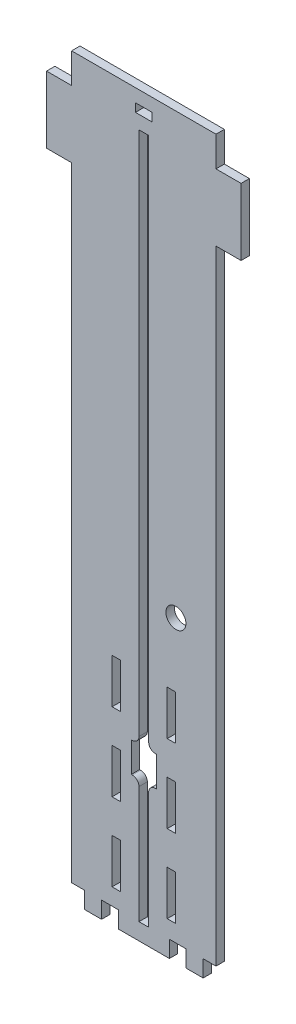
SolidWorks part; units mm, degrees
material "Acrylic (Medium-high impact)"
ref_plane "Front" through (0, 0, 0) normal (0, 0, 1) x (1, 0, 0)
ref_plane "Top" through (0, 0, 0) normal (0, 1, 0) x (1, 0, 0)
ref_plane "Right" through (0, 0, 0) normal (1, 0, 0) x (0, 0, -1)
sketch "Sketch1" plane through (0, 0, 0) normal (0, 0, 1) x (1, 0, 0)
  line L0 (0, 130.302) -> (0, -130.302) construction
  line L1 (-1.8415, 130.302) -> (-1.8415, -130.302)
  line L2 (-1.8415, -130.302) -> (1.8415, -130.302)
  line L3 (1.8415, 130.302) -> (1.8415, -130.302)
  line L4 (1.8415, 130.302) -> (-1.8415, 130.302)
  line L8 (-27.432, 143.51) -> (27.432, 143.51)
  line L9 (-27.432, 143.51) -> (-27.432, -136.652)
  line L10 (-27.432, -136.652) -> (27.432, -136.652)
  line L11 (27.432, 143.51) -> (27.432, -136.652)
  point P2 (0, -130.302)
  point P7 (0, 143.51)
  point P11 (0, 0)
  dimension "D1" = 3.683
  dimension "D4" = 260.604
  dimension "D7" = 6.35
  dimension "D2" = 54.864
  dimension "D3" = 273.812
extrude "Boss-Extrude1" add sketch "Sketch1" along normal blind 3.175
sketch "Sketch2" plane through (27.432, 0, 0) normal (1, 0, 0) x (0, 0, -1)
  line L0 (-3.175, -136.652) -> (-3.175, 143.51) construction
  line L1 (-3.175, -35.052) -> (228.6, -35.052)
  line L2 (-3.175, -35.052) -> (-3.175, -136.652)
  line L3 (-3.175, -136.652) -> (228.6, -136.652)
  line L4 (228.6, -35.052) -> (228.6, -136.652)
  line L5 (14.4, -88.392) -> (14.4, -83.312)
  line L6 (36.4, -83.312) -> (36.4, -88.392)
  line L7 (8.4, -103.892) -> (8.4, -98.812)
  line L8 (11.4, -103.892) -> (11.4, -98.812)
  line L9 (8.4, -72.892) -> (8.4, -67.812)
  line L10 (11.4, -72.892) -> (11.4, -67.812)
  line L11 (25.4, -83.312) -> (25.4, -88.392) construction
  line L12 (42.4, -103.892) -> (42.4, -98.812)
  line L13 (39.4, -103.892) -> (39.4, -98.812)
  line L14 (39.4, -72.892) -> (39.4, -67.812)
  line L15 (42.4, -72.892) -> (42.4, -67.812)
  line L16 (0, -136.652) -> (0, 143.51) construction
  line L17 (227.0125, -47.752) -> (227.0125, -64.6853) construction
  line L18 (228.6, -35.052) -> (225.425, -35.052)
  line L19 (228.6, -35.052) -> (228.6, -47.752)
  line L20 (228.6, -47.752) -> (225.425, -47.752)
  line L21 (225.425, -35.052) -> (225.425, -47.752)
  line L22 (228.6, -94.3187) -> (225.425, -94.3187)
  line L23 (228.6, -94.3187) -> (228.6, -107.0187)
  line L24 (228.6, -107.0187) -> (225.425, -107.0187)
  line L25 (225.425, -94.3187) -> (225.425, -107.0187)
  line L26 (228.6, -123.952) -> (225.425, -123.952)
  line L27 (228.6, -123.952) -> (228.6, -136.652)
  line L28 (228.6, -136.652) -> (225.425, -136.652)
  line L29 (225.425, -123.952) -> (225.425, -136.652)
  line L30 (228.6, -64.6853) -> (225.425, -64.6853)
  line L31 (228.6, -64.6853) -> (228.6, -77.3853)
  line L32 (228.6, -77.3853) -> (225.425, -77.3853)
  line L33 (225.425, -64.6853) -> (225.425, -77.3853)
  line L34 (227.0125, -77.3853) -> (227.0125, -94.3187) construction
  line L35 (227.0125, -107.0187) -> (227.0125, -123.952) construction
  arc A0 (14.4, -88.392) -> (36.4, -88.392) centre (25.4, -88.392) ccw
  arc A1 (36.4, -83.312) -> (14.4, -83.312) centre (25.4, -83.312) ccw
  arc A2 (8.4, -103.892) -> (11.4, -103.892) centre (9.9, -103.892) ccw
  arc A3 (11.4, -98.812) -> (8.4, -98.812) centre (9.9, -98.812) ccw
  arc A4 (8.4, -72.892) -> (11.4, -72.892) centre (9.9, -72.892) ccw
  arc A5 (11.4, -67.812) -> (8.4, -67.812) centre (9.9, -67.812) ccw
  arc A6 (42.4, -103.892) -> (39.4, -103.892) centre (40.9, -103.892) cw
  arc A7 (39.4, -98.812) -> (42.4, -98.812) centre (40.9, -98.812) cw
  arc A8 (42.4, -72.892) -> (39.4, -72.892) centre (40.9, -72.892) cw
  arc A9 (39.4, -67.812) -> (42.4, -67.812) centre (40.9, -67.812) cw
  point P44 (25.4, -85.852)
  point P47 (-3.175, -85.852)
  line M17 (0, -136.652) -> (0, 143.51)
  line M19 (-3.175, 143.51) -> (-3.175, -136.652)
  line M20 (-3.175, -136.652) -> (0, -136.652)
  dimension "D1" = 22
  dimension "D6" = 1.5
  dimension "D10" = 1.5
  dimension "D2" = 5.08
  dimension "D3" = 5.08
  dimension "D4" = 15.5
  dimension "D5" = 15.5
  dimension "D7" = 15.5
  dimension "D8" = 15.5
  dimension "D9" = 5.08
  dimension "D11" = 25.4
  dimension "D12" = 50.8
  dimension "D13" = 203.2
  dimension "D14" = 12.7
  dimension "D15" = 3.175
extrude "Boss-Extrude2" add sketch "Sketch2" against normal blind 3.175 contours L33 L30 L4 L20 L21 L1 L3 L29 L26 L24 L25 L22 L32 A5 L10 A4 L9 A3 L8 A2 L7 A1 L6 A0 L5 L13 A7 L12 A6 L14 A9 L15 A8 M17 | L1 M19 M20 M17 region at (27.432, -85.852, -115.7892) region at (27.432, -85.852, 1.5875)
sketch "Sketch3" plane through (24.257, 0, 0) normal (-1, 0, 0) x (0, 0, 1)
  line L0 (-225.425, -123.952) -> (-225.425, -136.652) construction
  line L1 (-225.425, -130.302) -> (0, -130.302)
  line L2 (-225.425, -130.302) -> (-225.425, -136.652)
  line L3 (-225.425, -136.652) -> (0, -136.652)
  line L4 (0, -130.302) -> (0, -136.652)
  dimension "D1" = 6.35
extrude "Boss-Extrude3" add sketch "Sketch3" along normal up to surface (51.689 mm away) up to face at (-27.432, 3.429, 1.5875)
sketch "Sketch4" plane through (0, -136.652, 0) normal (0, -1, 0) x (1, 0, 0)
  line L0 (22.5425, -23.8125) -> (22.5425, -36.5125)
  line L1 (27.432, 3.175) -> (22.5425, 3.175)
  line L2 (27.432, 3.175) -> (27.432, -9.525)
  line L3 (27.432, -9.525) -> (22.5425, -9.525)
  line L4 (22.5425, 3.175) -> (22.5425, -9.525)
  line L5 (27.432, -23.8125) -> (22.5425, -23.8125)
  line L6 (27.432, -23.8125) -> (27.432, -36.5125)
  line L7 (27.432, -36.5125) -> (22.5425, -36.5125)
  line L8 (22.5425, -50.8) -> (22.5425, -63.5)
  line L9 (27.432, -50.8) -> (22.5425, -50.8)
  line L10 (27.432, -50.8) -> (27.432, -63.5)
  line L11 (27.432, -63.5) -> (22.5425, -63.5)
  line L12 (22.5425, -77.7875) -> (22.5425, -90.4875)
  line L13 (27.432, -77.7875) -> (22.5425, -77.7875)
  line L14 (27.432, -77.7875) -> (27.432, -90.4875)
  line L15 (27.432, -90.4875) -> (22.5425, -90.4875)
  line L16 (22.5425, -104.775) -> (22.5425, -117.475)
  line L17 (27.432, -104.775) -> (22.5425, -104.775)
  line L18 (27.432, -104.775) -> (27.432, -117.475)
  line L19 (27.432, -117.475) -> (22.5425, -117.475)
  line L20 (22.5425, -131.7625) -> (22.5425, -144.4625)
  line L21 (27.432, -131.7625) -> (22.5425, -131.7625)
  line L22 (27.432, -131.7625) -> (27.432, -144.4625)
  line L23 (27.432, -144.4625) -> (22.5425, -144.4625)
  line L24 (22.5425, -158.75) -> (22.5425, -171.45)
  line L25 (27.432, -158.75) -> (22.5425, -158.75)
  line L26 (27.432, -158.75) -> (27.432, -171.45)
  line L27 (27.432, -171.45) -> (22.5425, -171.45)
  line L28 (22.5425, -185.7375) -> (22.5425, -198.4375)
  line L29 (27.432, -185.7375) -> (22.5425, -185.7375)
  line L30 (27.432, -185.7375) -> (27.432, -198.4375)
  line L31 (27.432, -198.4375) -> (22.5425, -198.4375)
  line L32 (22.5425, -212.725) -> (22.5425, -225.425)
  line L33 (27.432, -212.725) -> (22.5425, -212.725)
  line L34 (27.432, -212.725) -> (27.432, -225.425)
  line L35 (27.432, -225.425) -> (22.5425, -225.425)
  line L36 (0, 3.175) -> (0, -225.425) construction
  line L37 (-27.432, 3.175) -> (27.432, 3.175) construction
  line L38 (-27.432, -225.425) -> (27.432, -225.425) construction
  line L39 (-22.5425, 3.175) -> (-22.5425, -225.425)
  line L40 (27.432, 3.175) -> (22.5425, 3.175)
  line L41 (27.432, 3.175) -> (27.432, -225.425)
  line L42 (27.432, -225.425) -> (22.5425, -225.425)
  line L43 (22.5425, 3.175) -> (22.5425, -225.425)
  line L44 (-27.432, -225.425) -> (-22.5425, -225.425)
  line L45 (-27.432, 3.175) -> (-27.432, -225.425)
  line L46 (-27.432, 3.175) -> (-22.5425, 3.175)
  line L47 (-27.432, -225.425) -> (-22.5425, -225.425)
  line L48 (-27.432, -212.725) -> (-27.432, -225.425)
  line L49 (-27.432, -212.725) -> (-22.5425, -212.725)
  line L50 (-22.5425, -212.725) -> (-22.5425, -225.425)
  line L51 (-27.432, -198.4375) -> (-22.5425, -198.4375)
  line L52 (-27.432, -185.7375) -> (-27.432, -198.4375)
  line L53 (-27.432, -185.7375) -> (-22.5425, -185.7375)
  line L54 (-22.5425, -185.7375) -> (-22.5425, -198.4375)
  line L55 (-27.432, -171.45) -> (-22.5425, -171.45)
  line L56 (-27.432, -158.75) -> (-27.432, -171.45)
  line L57 (-27.432, -158.75) -> (-22.5425, -158.75)
  line L58 (-22.5425, -158.75) -> (-22.5425, -171.45)
  line L59 (-27.432, -144.4625) -> (-22.5425, -144.4625)
  line L60 (-27.432, -131.7625) -> (-27.432, -144.4625)
  line L61 (-27.432, -131.7625) -> (-22.5425, -131.7625)
  line L62 (-22.5425, -131.7625) -> (-22.5425, -144.4625)
  line L63 (-27.432, -117.475) -> (-22.5425, -117.475)
  line L64 (-27.432, -104.775) -> (-27.432, -117.475)
  line L65 (-27.432, -104.775) -> (-22.5425, -104.775)
  line L66 (-22.5425, -104.775) -> (-22.5425, -117.475)
  line L67 (-27.432, -90.4875) -> (-22.5425, -90.4875)
  line L68 (-27.432, -77.7875) -> (-27.432, -90.4875)
  line L69 (-27.432, -77.7875) -> (-22.5425, -77.7875)
  line L70 (-22.5425, -77.7875) -> (-22.5425, -90.4875)
  line L71 (-27.432, -63.5) -> (-22.5425, -63.5)
  line L72 (-27.432, -50.8) -> (-27.432, -63.5)
  line L73 (-27.432, -50.8) -> (-22.5425, -50.8)
  line L74 (-22.5425, -50.8) -> (-22.5425, -63.5)
  line L75 (-27.432, -36.5125) -> (-22.5425, -36.5125)
  line L76 (-27.432, -23.8125) -> (-27.432, -36.5125)
  line L77 (-27.432, -23.8125) -> (-22.5425, -23.8125)
  line L78 (-22.5425, 3.175) -> (-22.5425, -9.525)
  line L79 (-27.432, -9.525) -> (-22.5425, -9.525)
  line L80 (-27.432, 3.175) -> (-27.432, -9.525)
  line L81 (-27.432, 3.175) -> (-22.5425, 3.175)
  line L82 (-22.5425, -23.8125) -> (-22.5425, -36.5125)
  line L83 (-9.7155, 1.5875) -> (9.7155, 1.5875) construction
  line L85 (-27.432, 3.175) -> (-22.1615, 3.175)
  line L86 (-27.432, 3.175) -> (-27.432, 0)
  line L87 (-27.432, 0) -> (-22.1615, 0)
  line L88 (-22.1615, 3.175) -> (-22.1615, 0)
  line L92 (22.1615, 3.175) -> (22.1615, 0)
  line L93 (22.1615, 3.175) -> (27.432, 3.175)
  line L94 (27.432, 3.175) -> (27.432, 0)
  line L95 (22.1615, 0) -> (27.432, 0)
  line L96 (-27.432, 3.175) -> (27.432, 3.175)
  line L97 (-27.432, 3.175) -> (-27.432, 0)
  line L98 (-27.432, 0) -> (27.432, 0)
  line L99 (27.432, 3.175) -> (27.432, 0)
  line L100 (-2.6353, 3.175) -> (-2.6352, 0) [skipped]
  line L101 (-2.6352, 0) -> (2.6352, 0) [skipped]
  line L102 (2.6353, 3.175) -> (2.6352, 0) [skipped]
  line L103 (-2.6353, 3.175) -> (2.6353, 3.175) [skipped]
  line L104 (-9.7155, 0) -> (-16.0655, 0)
  line L105 (-9.7155, 0) -> (-9.7155, 3.175)
  line L106 (-9.7155, 3.175) -> (-16.0655, 3.175)
  line L107 (-16.0655, 0) -> (-16.0655, 3.175)
  line L111 (9.7155, 3.175) -> (16.0655, 3.175)
  line L112 (9.7155, 3.175) -> (9.7155, 0)
  line L113 (9.7155, 0) -> (16.0655, 0)
  line L114 (16.0655, 3.175) -> (16.0655, 0)
  point P86 (0, 1.5875)
  line M39 (27.432, 3.175) -> (-27.432, 3.175)
  line M40 (-27.432, 3.175) -> (-27.432, -225.425)
  dimension "D7" = 6.35
  dimension "D2" = 12.7
  dimension "D4" = 3.175
  dimension "D8" = 6.35
  dimension "D1" = 6.477
  dimension "D5" = 19.431
  dimension "D9" = 6.096
  dimension "D3" = 9
  dimension "D6" = 3
sketch "Sketch6" plane through (0, 0, 3.175) normal (0, 0, 1) x (1, 0, 0)
  line L1 (27.432, -47.752) -> (24.257, -47.752)
  line L2 (27.432, -47.752) -> (27.432, -64.6853)
  line L3 (27.432, -64.6853) -> (24.257, -64.6853)
  line L4 (24.257, -47.752) -> (24.257, -64.6853)
  line L5 (27.432, -77.3853) -> (24.257, -77.3853)
  line L6 (27.432, -77.3853) -> (27.432, -94.3187)
  line L7 (27.432, -94.3187) -> (24.257, -94.3187)
  line L8 (24.257, -77.3853) -> (24.257, -94.3187)
  line L9 (27.432, -107.0187) -> (24.257, -107.0187)
  line L10 (27.432, -107.0187) -> (27.432, -123.952)
  line L11 (27.432, -123.952) -> (24.257, -123.952)
  line L12 (24.257, -107.0187) -> (24.257, -123.952)
sketch "Sketch7" plane through (27.432, 0, 0) normal (1, 0, 0) x (0, 0, -1)
  line L0 (0, -35.052) -> (0, 143.51) construction
  line L1 (0, -8.6302) -> (327.0227, -8.6302)
  line L2 (0, -8.6302) -> (0, -288.0659)
  line L3 (0, -288.0659) -> (327.0227, -288.0659)
  line L4 (327.0227, -8.6302) -> (327.0227, -288.0659)
extrude "Cut-Extrude1" cut sketch "Sketch7" against normal through all
extrude "Cut-Extrude2" cut sketch "Sketch4" against normal blind 6.35 contours L107 L98 L105 L96 | L4 L95 L41 M39 | L87 L39 M40 M39 | L114 L96 L112 L98 region at (24.9873, -136.652, 1.5875) region at (12.8905, -136.652, 1.5875) region at (-12.8905, -136.652, 1.5875) region at (-24.9873, -136.652, 1.5875)
extrude "Cut-Extrude3" [suppressed] cut sketch "Sketch6" against normal through all
sketch "Sketch8" plane through (0, 0, 3.175) normal (0, 0, 1) x (1, 0, 0)
  line L0 (-27.432, 143.51) -> (-27.432, -130.302) construction
  line L1 (-27.432, 132.08) -> (-36.957, 132.08)
  line L2 (-27.432, 132.08) -> (-27.432, 106.68)
  line L3 (-27.432, 106.68) -> (-36.957, 106.68)
  line L4 (-36.957, 132.08) -> (-36.957, 106.68)
  line L5 (27.432, -130.302) -> (27.432, 143.51) construction
  line L6 (27.432, 132.08) -> (36.957, 132.08)
  line L7 (27.432, 132.08) -> (27.432, 106.68)
  line L8 (27.432, 106.68) -> (36.957, 106.68)
  line L9 (36.957, 132.08) -> (36.957, 106.68)
  line L10 (27.432, 143.51) -> (-27.432, 143.51) construction
  dimension "D1" = 9.525
  dimension "D2" = 25.4
  dimension "D3" = 11.43
extrude "Boss-Extrude4" add sketch "Sketch8" against normal up to surface (3.175 mm away) up to face at (0, 0, 0)
sketch "Sketch9" plane through (0, 0, 3.175) normal (0, 0, 1) x (1, 0, 0)
  line L0 (-8.89, -56.2187) -> (8.89, -56.2187) construction
  line L1 (-12.065, -47.752) -> (-8.89, -47.752)
  line L2 (-12.065, -47.752) -> (-12.065, -64.6853)
  line L3 (-12.065, -64.6853) -> (-8.89, -64.6853)
  line L4 (-8.89, -47.752) -> (-8.89, -64.6853)
  line L6 (-12.065, -77.3853) -> (-8.89, -77.3853)
  line L7 (-12.065, -77.3853) -> (-12.065, -94.3187)
  line L8 (-12.065, -94.3187) -> (-8.89, -94.3187)
  line L9 (-8.89, -77.3853) -> (-8.89, -94.3187)
  line L10 (-12.065, -107.0187) -> (-8.89, -107.0187)
  line L11 (-12.065, -107.0187) -> (-12.065, -123.952)
  line L12 (-12.065, -123.952) -> (-8.89, -123.952)
  line L13 (-8.89, -107.0187) -> (-8.89, -123.952)
  line L14 (8.89, -47.752) -> (12.065, -47.752)
  line L15 (8.89, -47.752) -> (8.89, -64.6853)
  line L16 (8.89, -64.6853) -> (12.065, -64.6853)
  line L18 (27.432, -47.752) -> (24.257, -47.752) construction
  line L19 (24.257, -47.752) -> (24.257, -64.6853) construction
  line L20 (-1.8415, -130.302) -> (1.8415, -130.302) construction
  line L21 (12.065, -47.752) -> (12.065, -64.6853)
  line L22 (8.89, -77.3853) -> (12.065, -77.3853)
  line L23 (8.89, -77.3853) -> (8.89, -94.3187)
  line L24 (8.89, -94.3187) -> (12.065, -94.3187)
  line L25 (12.065, -77.3853) -> (12.065, -94.3187)
  line L26 (8.89, -107.0187) -> (12.065, -107.0187)
  line L27 (8.89, -107.0187) -> (8.89, -123.952)
  line L28 (8.89, -123.952) -> (12.065, -123.952)
  line L29 (12.065, -107.0187) -> (12.065, -123.952)
  line L31 (-22.5425, -130.302) -> (-27.432, -130.302) construction
  line L32 (-10.4775, -94.3187) -> (-10.4775, -107.0187) construction
  line L33 (-10.4775, -77.3853) -> (-10.4775, -64.6853) construction
  point P26 (0, -56.2187)
  point P36 (0, -130.302)
  dimension "D1" = 17.78
  dimension "D3" = 6.35
  dimension "D4" = 12.7
extrude "Cut-Extrude4" cut sketch "Sketch9" against normal through all
sketch "Sketch10" plane through (0, 0, 3.175) normal (0, 0, 1) x (1, 0, 0)
  line L0 (-27.432, 132.08) -> (-36.957, 132.08) construction
  line L1 (-3.175, 138.557) -> (3.175, 138.557)
  line L2 (-3.175, 138.557) -> (-3.175, 135.382)
  line L3 (-3.175, 135.382) -> (3.175, 135.382)
  line L4 (3.175, 138.557) -> (3.175, 135.382)
  line L5 (27.432, 143.51) -> (-27.432, 143.51) construction
  point P6 (0, 135.382)
  point P9 (0, 143.51)
  dimension "D1" = 3.302
  dimension "D2" = 6.35
  dimension "D3" = 3.175
extrude "Cut-Extrude5" cut sketch "Sketch10" against normal through all
sketch "Sketch11" plane through (0, 0, 3.175) normal (0, 0, 1) x (1, 0, 0)
  line L0 (27.432, -130.302) -> (22.5425, -130.302) construction
  line L1 (-2.8575, -71.882) -> (2.8575, -71.882)
  line L2 (-2.8575, -71.882) -> (-2.8575, -79.502)
  line L3 (-2.8575, -79.502) -> (2.8575, -79.502)
  line L4 (2.8575, -71.882) -> (2.8575, -79.502)
  line L5 (-1.8415, -130.302) -> (1.8415, -130.302) construction
  point P9 (0, -71.882)
  point P12 (0, -130.302)
  dimension "D1" = 7.62
  dimension "D2" = 50.8
  dimension "D3" = 5.715
extrude "Cut-Extrude6" [suppressed] cut sketch "Sketch11" against normal through all
sketch "Sketch12" plane through (0, 0, 3.175) normal (0, 0, 1) x (1, 0, 0)
  line L0 (-22.5425, -130.302) -> (-27.432, -130.302) construction
  line L1 (-22.5425, -136.652) -> (-16.0655, -136.652)
  line L2 (-22.5425, -136.652) -> (-22.5425, -137.16)
  line L3 (-22.5425, -137.16) -> (-16.0655, -137.16)
  line L4 (-16.0655, -136.652) -> (-16.0655, -137.16)
  line L5 (-9.7155, -136.652) -> (9.7155, -136.652)
  line L6 (-9.7155, -136.652) -> (-9.7155, -137.16)
  line L7 (-9.7155, -137.16) -> (9.7155, -137.16)
  line L8 (22.5425, -136.652) -> (22.5425, -137.16)
  line L9 (16.0655, -130.302) -> (16.0655, -136.652) construction
  line L11 (9.7155, -136.652) -> (9.7155, -137.16)
  line L13 (16.0655, -136.652) -> (16.0655, -137.16)
  line L14 (16.0655, -136.652) -> (22.5425, -136.652)
  line L15 (16.0655, -137.16) -> (22.5425, -137.16)
  dimension "D1" = 6.858
extrude "Boss-Extrude5" [suppressed] add sketch "Sketch12" against normal up to surface (2.9972 mm away) up to face at (0, 136.9695, 0)
sketch "Sketch13" plane through (0, 0, 3.175) normal (0, 0, 1) x (1, 0, 0)
  line L0 (-9.7155, -136.652) -> (9.7155, -136.652) construction
  line L1 (-4.7625, -71.882) -> (4.7625, -71.882)
  line L2 (-4.7625, -71.882) -> (-4.7625, -83.312)
  line L3 (-4.7625, -83.312) -> (4.7625, -83.312)
  line L4 (4.7625, -71.882) -> (4.7625, -83.312)
  line L5 (-1.8415, -130.302) -> (1.8415, -130.302) construction
  point P10 (0, -71.882)
  point P13 (0, -130.302)
  dimension "D1" = 53.34
  dimension "D2" = 64.77
  dimension "D3" = 9.525
extrude "Cut-Extrude7" cut sketch "Sketch13" against normal through all
sketch "Sketch14" plane through (0, 0, 3.175) normal (0, 0, 1) x (1, 0, 0)
  line L0 (16.0655, -130.302) -> (9.7155, -130.302) construction
  line L1 (27.432, -130.302) -> (27.432, 106.68) construction
  circle A0 centre (12.192, -23.3172) radius 3.81
  dimension "D3" = 7.62
  dimension "D1" = 106.9848
  dimension "D2" = 15.24
extrude "Cut-Extrude8" cut sketch "Sketch14" against normal through all
fillet "Fillet1" radius 2.54 4 edges at (1.8415, -71.882, 1.5875) (-1.8415, -71.882, 1.5875) (1.8415, -83.312, 1.5875) (-1.8415, -83.312, 1.5875)
sketch "Sketch15" plane through (0, 0, 3.175) normal (0, 0, 1) x (1, 0, 0)
  line L0 (-36.957, 132.08) -> (-36.957, 106.68) construction
  line L1 (-36.957, 143.51) -> (36.957, 143.51)
  line L2 (-36.957, 143.51) -> (-36.957, -21.7794)
  line L3 (-36.957, -21.7794) -> (36.957, -21.7794)
  line L4 (36.957, 143.51) -> (36.957, -21.7794)
  line L5 (36.957, 106.68) -> (36.957, 132.08) construction
  point P4 (-43.2144, 148.0457)
  point P6 (0, 0)
extrude "Cut-Extrude9" [suppressed] cut sketch "Sketch15" against normal through all
equation "\"bottomThickness\"= .25in"
equation "\"wallThickness\"= .125in"
equation "\"D7@Sketch1\"=\"bottomThickness\""
equation "\"D1@Boss-Extrude1\"=\"wallThickness\""
equation "\"D15@Sketch2\"=\"wallThickness\""
equation "\"D1@Boss-Extrude2\"=\"wallThickness\""
equation "\"D1@Sketch3\"=\"bottomThickness\""
equation "\"D4@Sketch4\"=\"wallThickness\""
equation "\"D1@Sketch10\"=\"wallThickness\"+.005"
equation "\"D1@Cut-Extrude2\"=\"bottomThickness\""
equation "\"D1@Sketch12\"=\"bottomThickness\"+.02"
